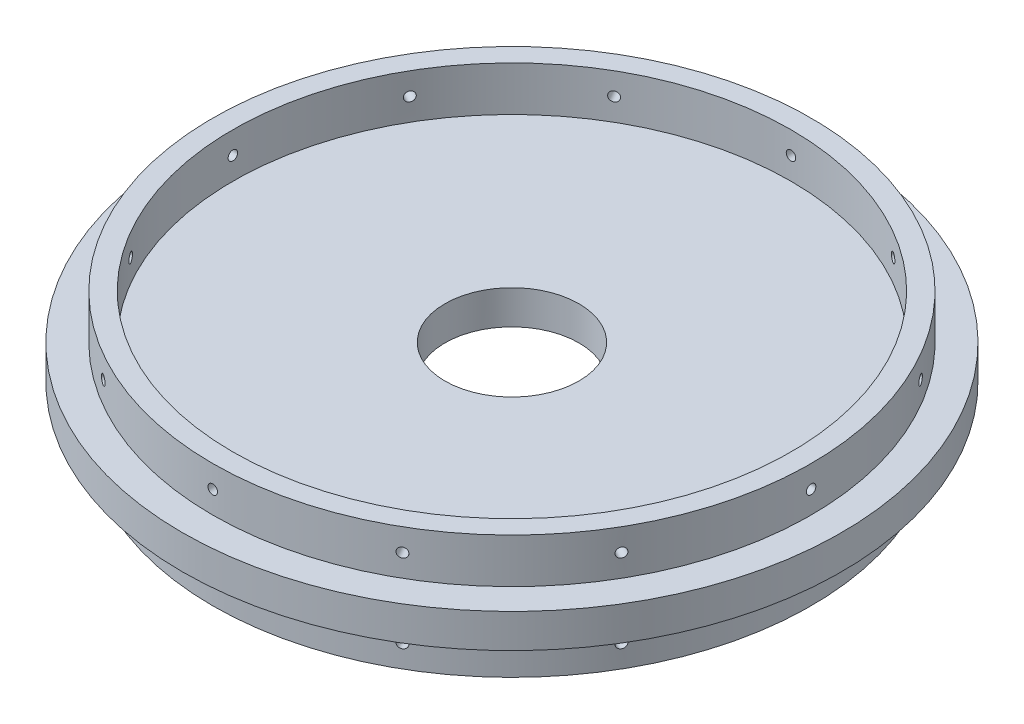
SolidWorks part; units mm, degrees
material "6061-T6 (SS)"
ref_plane "Front Plane" through (0, 0, 0) normal (0, 0, 1) x (1, 0, 0)
ref_plane "Top Plane" through (0, 0, 0) normal (0, 1, 0) x (1, 0, 0)
ref_plane "Right Plane" through (0, 0, 0) normal (1, 0, 0) x (0, 0, -1)
sketch "Sketch1" plane through (0, 0, 0) normal (0, 1, 0) x (1, 0, 0)
  circle A0 centre (0, 0) radius 93.726
  dimension "D1" = 187.452
extrude "Boss-Extrude1" add sketch "Sketch1" along normal mid plane 9.652
sketch "Sketch2" plane through (0, 0, 0) normal (0, 0, 1) x (1, 0, 0)
  line L0 (0, -18.3275) -> (0, 20.8308) construction
  line L1 (0, -4.826) -> (-25.4, -4.826)
  line L2 (-93.726, -4.826) -> (93.726, -4.826) construction
  line L3 (0, -4.826) -> (0, 1.27)
  spline S0 degree 3 poles (0, 1.27) (-5.1197, 1.5129) (-13.6852, -0.4966) (-22.1585, -2.9398) (-25.4, -4.826) knots 0 0 0 0 0.575799 1 1 1 1
  dimension "D1" = 25.4
  dimension "D2" = 6.096
revolve "Cut-Revolve1" [suppressed] cut sketch "Sketch2" angle 360 about L0
sketch "Sketch4" plane through (0, 4.826, 0) normal (0, 1, 0) x (1, 0, 0)
  circle A0 centre (0, 0) radius 85.09
  circle A1 centre (0, 0) radius 79.375
  dimension "D1" = 170.18
  dimension "D2" = 158.75
extrude "Boss-Extrude2" add sketch "Sketch4" along normal blind 12.7
ref_plane "Plane1" through (0, 0, -85.09) normal (0, 0, -1) x (-1, 0, 0)
sketch "Sketch5" plane through (0, 0, -85.09) normal (0, 0, -1) x (-1, 0, 0)
  line L0 (0, 19.2786) -> (0, -19.2786) construction
  line L1 (79.375, 17.526) -> (-79.375, 17.526) construction
  circle A0 centre (0, 11.176) radius 1.3525
  dimension "D1" = 2.7051
  dimension "D2" = 6.35
extrude "Cut-Extrude2" cut sketch "Sketch5" against normal blind 12.7
pattern_circular "CirPattern1" count 12 over 360 about axis through (0, 17.526, 0) along (0, -1, 0) of "Cut-Extrude2" reverse direction yes
mirror "Mirror2" about plane through (0, 0, 0) normal (0, 1, 0) of "CirPattern1", "Cut-Extrude2", "Boss-Extrude2"
sketch "Sketch6" plane through (0, 4.826, 0) normal (0, 1, 0) x (1, 0, 0)
  line L0 (-63.5, 0) -> (-69.85, 0)
  line L1 (0, -69.85) -> (0, -63.5)
  line L2 (0, -19.2786) -> (0, 19.2786) construction
  arc A0 (-69.85, 0) -> (0, -69.85) centre (0, 0) ccw
  arc A1 (-63.5, 0) -> (0, -63.5) centre (0, 0) ccw
  dimension "D1" = 69.85
  dimension "D2" = 63.5
  dimension "D3" = 90
extrude "Cut-Extrude3" [suppressed] cut sketch "Sketch6" against normal up to surface (9.652 mm away) up to face at (0, -4.826, 79.375)
sketch "Sketch7" plane through (0, -4.826, 0) normal (0, -1, 0) x (1, 0, 0)
  circle A0 centre (0, 0) radius 19.05
  dimension "D1" = 38.1
extrude "Cut-Extrude4" cut sketch "Sketch7" against normal through all
